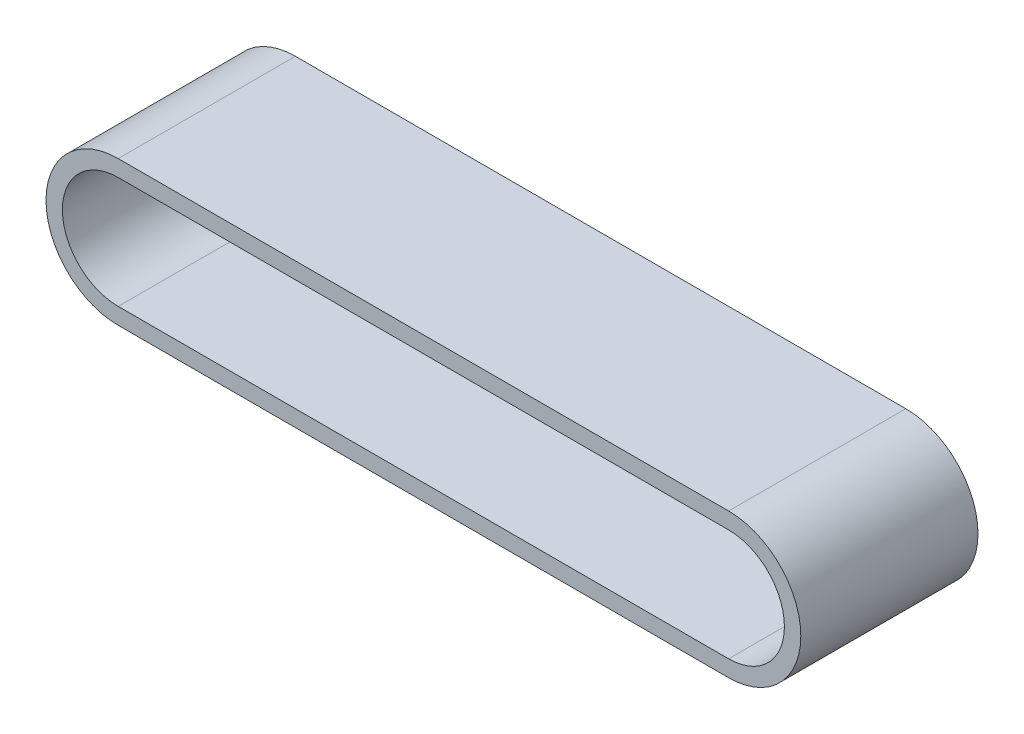
SolidWorks part; units mm, degrees
material "Silicon Rubber"
ref_plane "Front Plane" through (0, 0, 0) normal (0, 0, 1) x (1, 0, 0)
ref_plane "Top Plane" through (0, 0, 0) normal (0, 1, 0) x (1, 0, 0)
ref_plane "Right Plane" through (0, 0, 0) normal (1, 0, 0) x (0, 0, -1)
sketch "Sketch1" plane through (0, 0, 0) normal (0, 0, 1) x (1, 0, 0)
  line L0 (87.5, 0) -> (-87.5, 0) construction
  line L1 (87.5, -16) -> (-87.5, -16)
  line L2 (87.5, 16) -> (-87.5, 16)
  line L3 (87.5, -20.7) -> (-87.5, -20.7)
  line L4 (87.5, 20.7) -> (-87.5, 20.7)
  arc A0 (87.5, -16) -> (87.5, 16) centre (87.5, 0) ccw
  arc A1 (-87.5, 16) -> (-87.5, -16) centre (-87.5, 0) ccw
  arc A2 (-87.5, 20.7) -> (-87.5, -20.7) centre (-87.5, 0) ccw
  arc A3 (87.5, -20.7) -> (87.5, 20.7) centre (87.5, 0) ccw
  point P2 (0, 0)
  dimension "D1" = 16
  dimension "D2" = 175
  dimension "D3" = 4.7
extrude "Boss-Extrude1" add sketch "Sketch1" along normal blind 50.8
